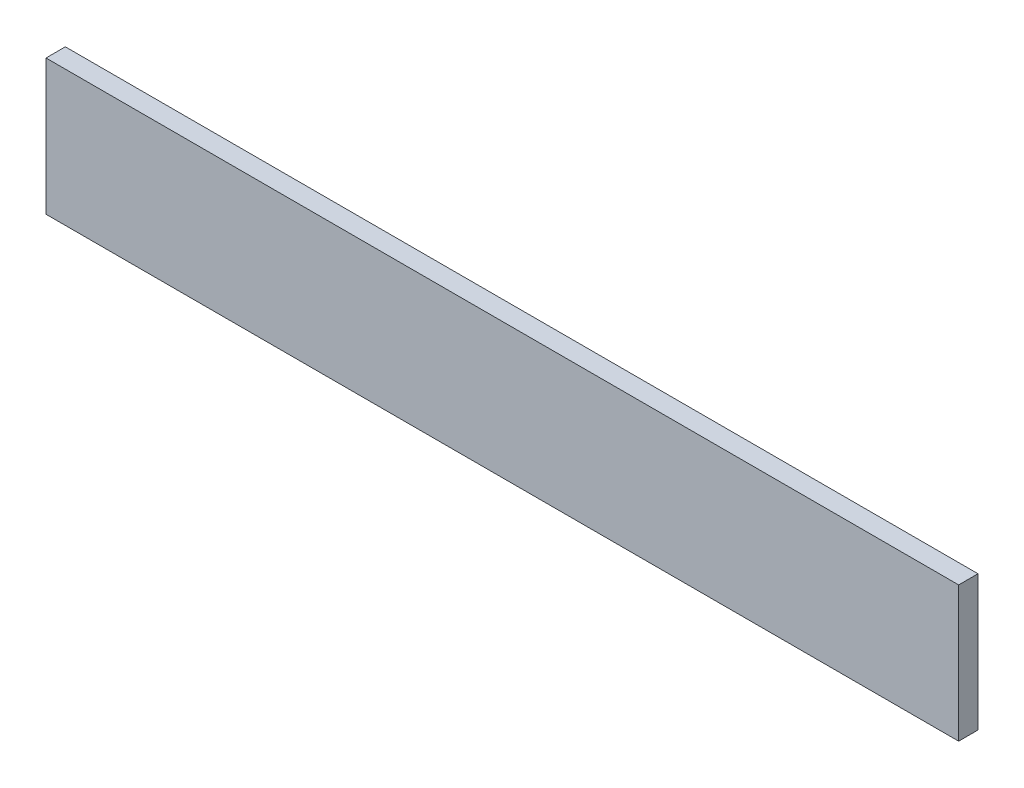
SolidWorks part; units mm, degrees
material "1.4016 (X6Cr17)"
ref_plane "前视基准面" through (0, 0, 0) normal (0, 0, 1) x (1, 0, 0)
ref_plane "上视基准面" through (0, 0, 0) normal (0, 1, 0) x (1, 0, 0)
ref_plane "右视基准面" through (0, 0, 0) normal (1, 0, 0) x (0, 0, -1)
sketch "草图1" plane through (0, 0, 0) normal (0, 0, 1) x (1, 0, 0)
  line L1 (-236, 35) -> (236, 35)
  line L2 (-236, 35) -> (-236, -35)
  line L3 (-236, -35) -> (236, -35)
  line L4 (236, 35) -> (236, -35)
  line L5 (-236, 35) -> (236, -35) construction
  line L6 (-236, -35) -> (236, 35) construction
  point P0 (0, 0)
  dimension "D1" = 70
  dimension "D2" = 472
base flange "基体-法兰1" sketch "草图1" thickness 10 reverse thickness direction no parameters "D1"=4
ref_plane "基准面1" through (0, 0, -5) normal (0, 0, 1) x (1, 0, 0)
sketch "折弯-线1" plane through (0, 0, 0) normal (0, 1, 0) x (1, 0, 0)
sketch "边界框1" plane through (0, 0, 0) normal (0, 1, 0) x (1, 0, 0)
sheet metal parameters "钣金(1)" thickness 10 parameters "D1"=4
flat pattern "平板型式(1)" [suppressed]
sketch "折弯-线2" plane through (0, 0, 0) normal (0, 1, 0) x (1, 0, 0)
sketch "边界框2" [suppressed] plane through (0, 0, 0) normal (0, 1, 0) x (1, 0, 0)
